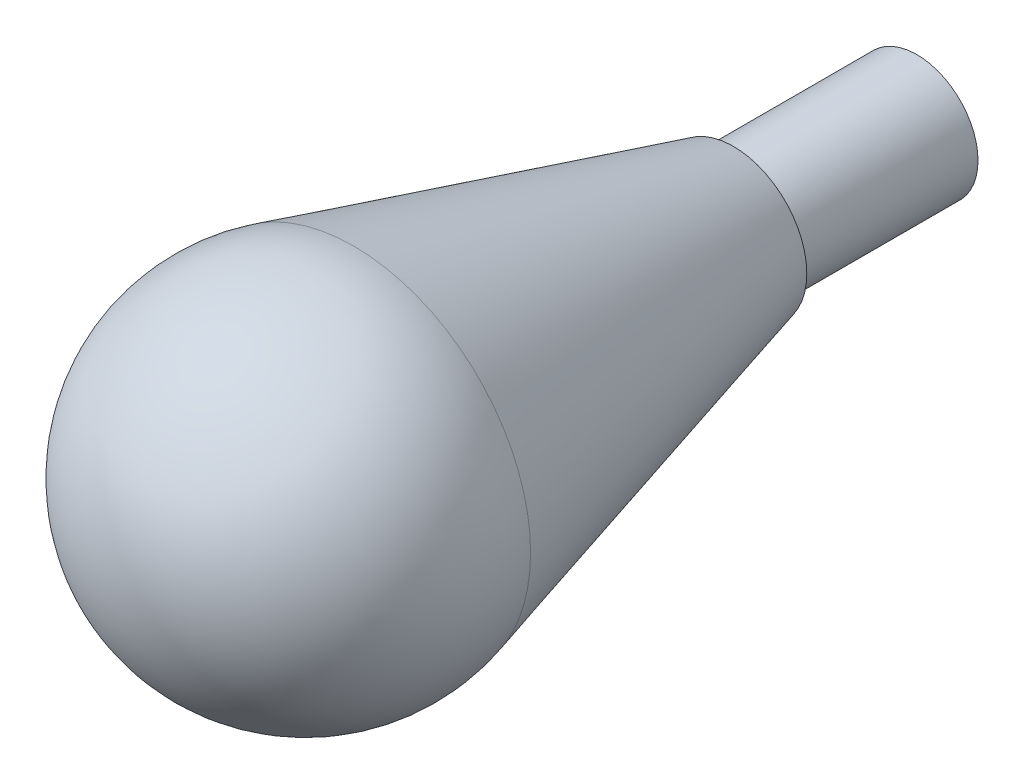
SolidWorks part; units mm, degrees
material "Ст 3 ГОСТ 380-88"
ref_plane "Front Plane" through (0, 0, 0) normal (0, 0, 1) x (1, 0, 0)
ref_plane "Top Plane" through (0, 0, 0) normal (0, 1, 0) x (1, 0, 0)
ref_plane "Right Plane" through (0, 0, 0) normal (1, 0, 0) x (0, 0, -1)
sketch "Sketch1" plane through (-0.63, -7.9619, 0) normal (0, 0, 1) x (1, 0, 0)
  circle A1 centre (0.63, 7.9619) radius 5
  point P1 (0, 0)
extrude "Boss-Extrude1" add sketch "Sketch1" along normal blind 15
ref_axis "Axis1" through (0, 0, 15) along (0, 0, -1)
sketch "Sketch2" plane through (0, 0, 0) normal (1, 0, 0) x (0, 0, -1)
  line L0 (-65, 0) -> (-15, 0)
  line L1 (-15, 0) -> (-8.4438, 0) construction
  line L2 (-15, 5) -> (-15, -5) construction
  line L3 (-15, 6) -> (-15, 0)
  line L4 (-46.0522, 14.4712) -> (-15, 6)
  arc A0 (-46.0522, 14.4712) -> (-65, 0) centre (-50, 0) ccw
  point P1 (0, 0)
  point P6 (-51.5435, -9.9255)
  point P8 (-51.5435, -9.9255)
  point P10 (0, 0)
  point P11 (-48.6527, 2.1835)
  point P12 (-33.2611, 0)
  point P13 (0, 0)
  point P14 (0, 0)
  dimension "D1" = 30
  dimension "D2" = 50
  dimension "D3" = 6
revolve "Revolve2" add sketch "Sketch2" angle 360 about L0
